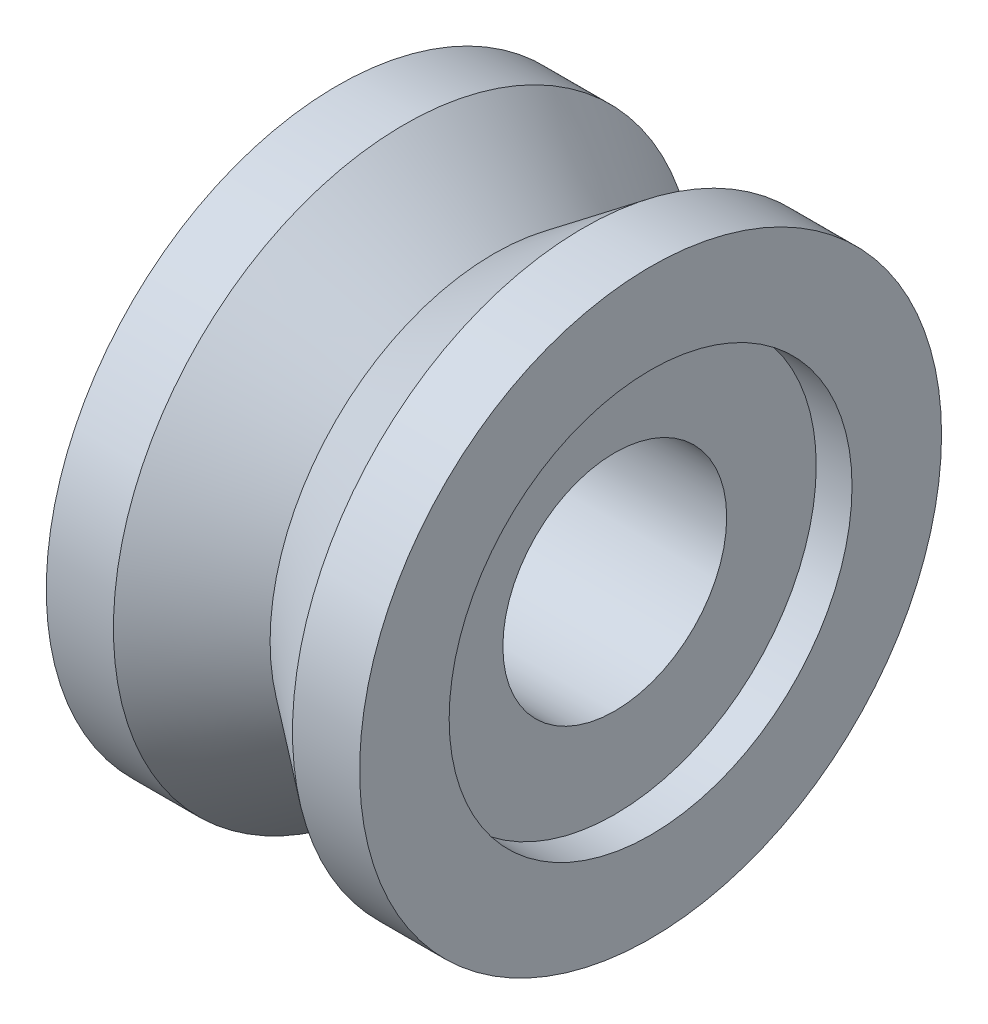
SolidWorks part; units mm, degrees
ref_plane "Front Plane" through (0, 0, 0) normal (0, 0, 1) x (1, 0, 0)
ref_plane "Top Plane" through (0, 0, 0) normal (0, 1, 0) x (1, 0, 0)
ref_plane "Right Plane" through (0, 0, 0) normal (1, 0, 0) x (0, 0, -1)
sketch "Sketch1" plane through (0, 0, 0) normal (1, 0, 0) x (0, 0, -1)
  circle A0 centre (0, 0) radius 6.5
  dimension "D1" = 13
extrude "Boss-Extrude1" add sketch "Sketch1" along normal mid plane 7
sketch "Sketch2" plane through (0, 0, 0) normal (0, 0, 1) x (1, 0, 0)
  line L0 (-2, 6.5) -> (0, 5)
  line L1 (0, 5) -> (2, 6.5)
  line L2 (3.5, 6.5) -> (-3.5, 6.5) construction
  line L3 (2, 6.5) -> (-2, 6.5)
  line L4 (0, 5) -> (0, 0) construction
  dimension "D1" = 4
  dimension "D2" = 1.5
revolve "Cut-Revolve1" cut sketch "Sketch2" angle 360 about axis through (3.5, 0, 0) along (-1, 0, 0)
sketch "Sketch4" plane through (3.5, 0, 0) normal (1, 0, 0) x (0, 0, -1)
  circle A0 centre (0, 0) radius 4.5
  dimension "D1" = 9
extrude "Cut-Extrude1" cut sketch "Sketch4" against normal blind 0.8
mirror "Mirror1" about plane through (0, 0, 0) normal (1, 0, 0) of "Cut-Extrude1"
sketch "Sketch5" plane through (0, 0, 0) normal (1, 0, 0) x (0, 0, -1)
  circle A0 centre (0, 0) radius 2.5
  dimension "D1" = 5
extrude "Cut-Extrude2" cut sketch "Sketch5" against normal through all both and the other way through all
ref_axis "Axis1" through (-2.7, 0, 0) along (1, 0, 0)
sketch "Sketch6" plane through (0, 0, 0) normal (0, 1, 0) x (1, 0, 0)
  line L0 (0, 5) -> (-2, 6.5) construction
  line L1 (2, 6.5) -> (0, 5) construction
  circle A0 centre (0, 6.875) radius 1.5
  dimension "D1" = 3
